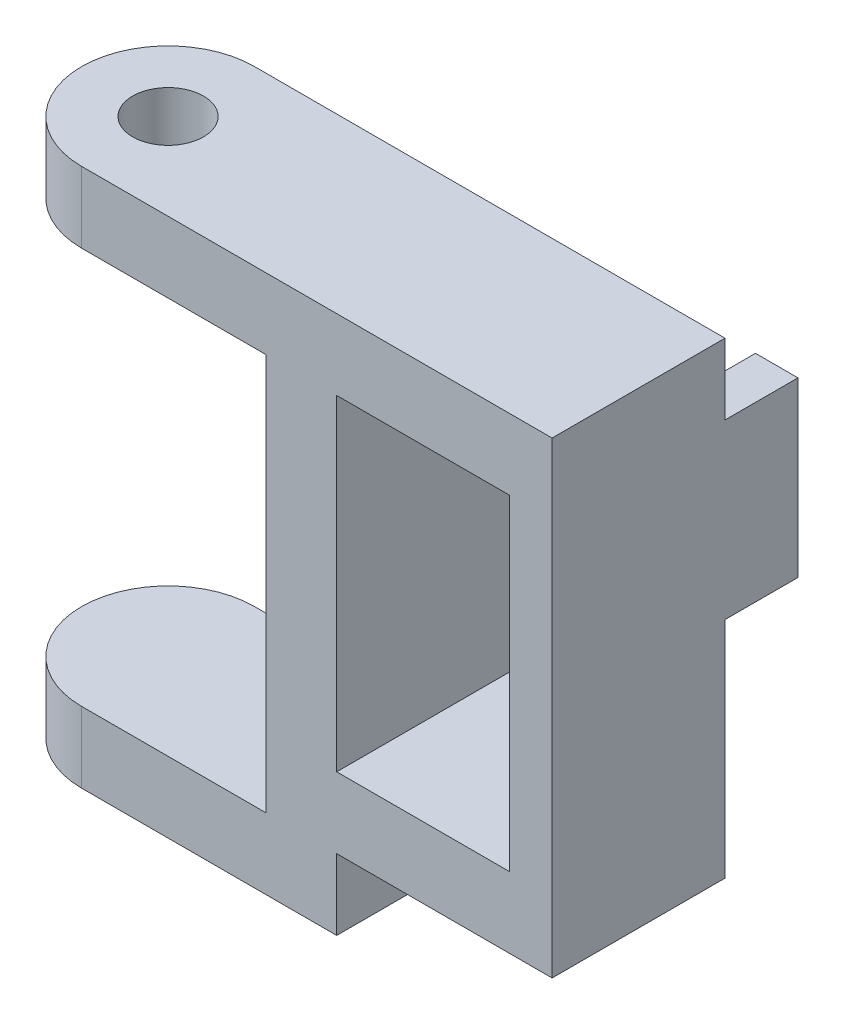
SolidWorks part; units mm, degrees
ref_plane "Front Plane" through (0, 0, 0) normal (0, 0, 1) x (1, 0, 0)
ref_plane "Top Plane" through (0, 0, 0) normal (0, 1, 0) x (1, 0, 0)
ref_plane "Right Plane" through (0, 0, 0) normal (1, 0, 0) x (0, 0, -1)
sketch "Sketch3" plane through (0, 0, 0) normal (0, 0, 1) x (1, 0, 0)
  line L0 (-40.4079, 21.4132) -> (-21.3079, 21.4132)
  line L1 (-21.3079, 21.4132) -> (-21.3079, -6.5868)
  line L2 (-21.3079, -6.5868) -> (-40.4079, -6.5868)
  line L3 (-40.4079, 26.4132) -> (-16.3079, 26.4132)
  line L4 (-16.3079, 26.4132) -> (-16.3079, -11.5868)
  line L5 (-16.3079, -11.5868) -> (-40.4079, -11.5868)
  line L6 (-40.4079, 26.4132) -> (-40.4079, 21.4132)
  line L7 (-40.4079, -6.5868) -> (-40.4079, -11.5868)
  dimension "D1" = 19.1
  dimension "D2" = 28
  dimension "D3" = 5
extrude "Boss-Extrude1" add sketch "Sketch3" along normal blind 12.2
sketch "Sketch4" plane through (0, 26.4132, 0) normal (0, 1, 0) x (1, 0, 0)
  line L0 (-40.4079, -6.1) -> (-34.3079, -6.1) construction
  line L1 (-40.4079, -12.2) -> (-40.4079, 0) construction
  line L4 (-16.3079, -12.2) -> (-40.4079, -12.2) construction
  line L5 (-16.3079, 0) -> (-40.4079, 0) construction
  arc A0 (-31.3079, -12.2) -> (-31.3079, 0) centre (-34.3079, -6.1) cw
  circle A1 centre (-34.3079, -6.1) radius 2.5
  dimension "D2" = 5
  dimension "D1" = 6.1
extrude "Cut-Extrude1" cut sketch "Sketch4" against normal blind 5 contours A1
sketch "Sketch5" plane through (0, 26.4132, 0) normal (0, 1, 0) x (1, 0, 0)
  line L0 (-40.4079, -6.1) -> (-34.3079, -6.1) construction
  line L1 (-40.4079, -12.2) -> (-40.4079, 0) construction
  line L2 (-34.3079, -6.1) -> (-34.3079, 0) construction
  line L3 (-16.3079, 0) -> (-40.4079, 0) construction
  line L4 (-34.3079, 0) -> (-34.3079, -12.2) construction
  line L5 (-16.3079, -12.2) -> (-40.4079, -12.2) construction
  arc A0 (-34.3079, -12.2) -> (-34.3079, 0) centre (-34.3079, -6.1) cw
  dimension "D1" = 6.1
extrude "Cut-Extrude2" cut sketch "Sketch5" against normal through all and the other way through all
sketch "Sketch6" plane through (0, -11.5868, 0) normal (0, -1, 0) x (1, 0, 0)
  line L0 (-34.3079, 12.2) -> (-34.3079, 6.1) construction
  circle A0 centre (-34.3079, 6.1) radius 2
  dimension "D2" = 4
  dimension "D1" = 6.1
extrude "Boss-Extrude2" add sketch "Sketch6" along normal blind 3 contours A0
sketch "Sketch7" plane through (-16.3079, 0, 0) normal (1, 0, 0) x (0, 0, -1)
  line L0 (-12.2, -11.5868) -> (-12.2, 26.4132) construction
  line L2 (0, -11.5868) -> (0, 26.4132) construction
  line L3 (-12.2, 26.4132) -> (0, 26.4132)
  line L4 (-12.2, 26.4132) -> (-12.2, 21.4141)
  line L5 (-12.2, 21.4141) -> (0, 21.4141)
  line L6 (0, 26.4132) -> (0, 21.4141)
  line L7 (-12.2, -6.5868) -> (0, -6.5868)
  line L8 (-12.2, -6.5868) -> (-12.2, -1.5868)
  line L9 (-12.2, -1.5868) -> (0, -1.5868)
  line L10 (0, -6.5868) -> (0, -1.5868)
  point P0 (-12.2, -6.5868)
  dimension "D1" = 4.9991
  dimension "D2" = 5
  dimension "D3" = 5
extrude "Boss-Extrude3" add sketch "Sketch7" along normal blind 15.2
sketch "Sketch9" plane through (0, 21.4141, 0) normal (0, -1, 0) x (1, 0, 0)
  line L0 (-1.1079, 12.2) -> (-16.3079, 12.2) construction
  line L1 (-1.1079, 0) -> (-4.1079, 0)
  line L2 (-1.1079, 0) -> (-1.1079, 12.2)
  line L3 (-1.1079, 12.2) -> (-4.1079, 12.2)
  line L4 (-4.1079, 0) -> (-4.1079, 12.2)
  dimension "D1" = 3
extrude "Boss-Extrude5" add sketch "Sketch9" along normal up to next contours L2 L1 L4 L3
sketch "Sketch10" plane through (0, 0, 0) normal (0, 0, -1) x (-1, 0, 0)
  line L0 (1.1079, -6.5868) -> (1.1079, 26.4132) construction
  line L1 (4.1079, 21.4141) -> (1.1079, 21.4141)
  line L2 (4.1079, 21.4141) -> (4.1079, 9.2141)
  line L3 (4.1079, 9.2141) -> (1.1079, 9.2141)
  line L4 (1.1079, 21.4141) -> (1.1079, 9.2141)
  dimension "D1" = 12.2
extrude "Boss-Extrude6" add sketch "Sketch10" along normal blind 5.15
